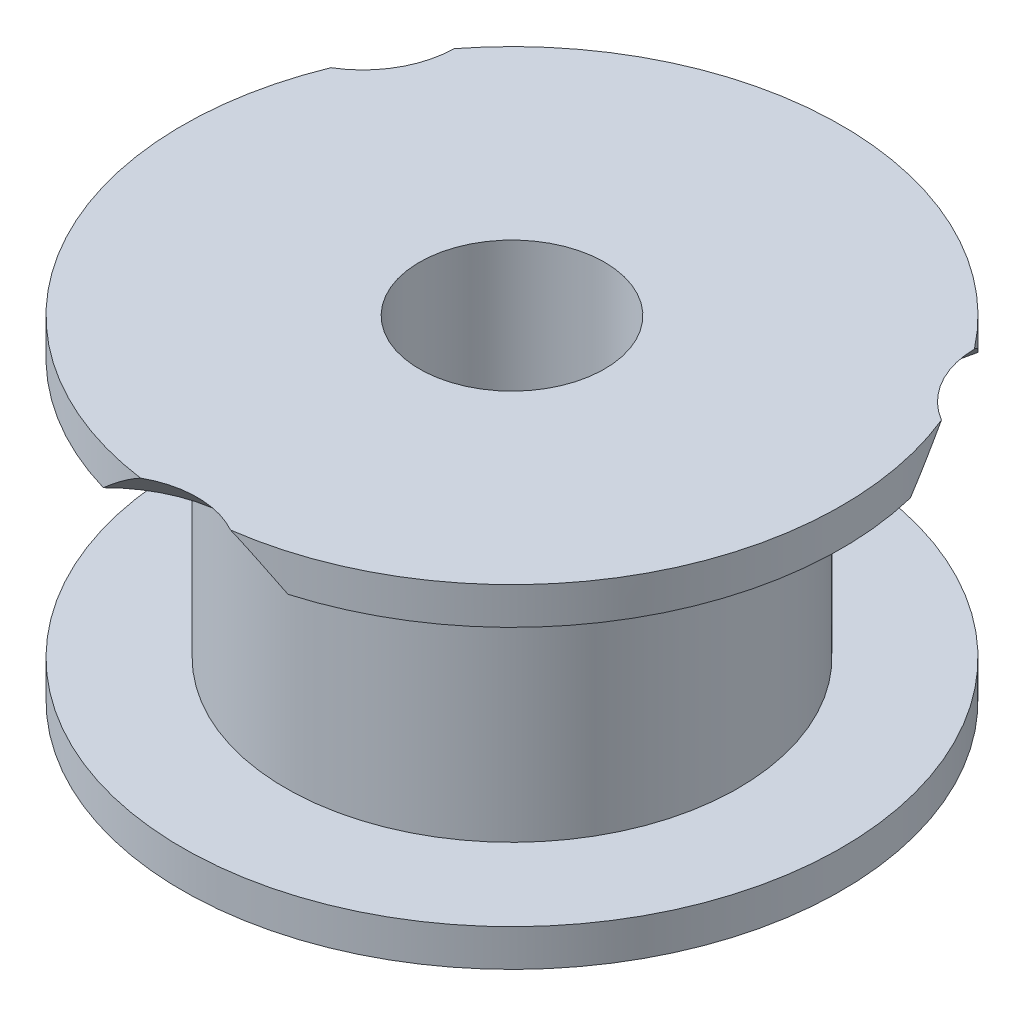
SolidWorks part; units mm, degrees
ref_plane "Face" through (0, 0, 0) normal (0, 0, 1) x (1, 0, 0)
ref_plane "Dessus" through (0, 0, 0) normal (0, 1, 0) x (1, 0, 0)
ref_plane "Droite" through (0, 0, 0) normal (1, 0, 0) x (0, 0, -1)
sketch "Esquisse1" plane through (0, 0, 0) normal (0, 0, 1) x (1, 0, 0)
  line L0 (0, 0) -> (0, 9.7978) construction
  line L1 (2.5, 0) -> (8.9, 0)
  line L2 (8.9, 0) -> (8.9, 1)
  line L3 (8.9, 1) -> (6.11, 1)
  line L4 (6.11, 1) -> (6.11, 8)
  line L5 (6.11, 8) -> (8.9, 8)
  line L6 (8.9, 8) -> (8.9, 9)
  line L9 (8.9, 9) -> (2.5, 9)
  line L10 (2.5, 9) -> (2.5, 0)
  dimension "D1" = 2.5
  dimension "D2" = 7
  dimension "D3" = 8.9
  dimension "D4" = 6.11
  dimension "D5" = 9
  dimension "D6" = 1
revolve "Révolution1" add sketch "Esquisse1" angle 360 about L0
sketch "Esquisse2" plane through (0, 8, 0) normal (0, -1, 0) x (1, 0, 0)
  circle A0 centre (0, 0) radius 11 construction
  circle A1 centre (0, 11) radius 2.5
  circle A2 centre (9.5263, -5.5) radius 2.5
  circle A3 centre (-9.5263, -5.5) radius 2.5
  point P12 (0, 0)
  dimension "D1" = 5
  dimension "D2" = 22
  dimension "D3" = 3
extrude "Enlèv. mat.-Extru.1" cut sketch "Esquisse2" against normal up to next
chamfer "Chanfrein1" distance 1 angle 45 3 edges at (7.3612, 8, -4.25) (0, 8, 8.5) (-7.3612, 8, -4.25)
